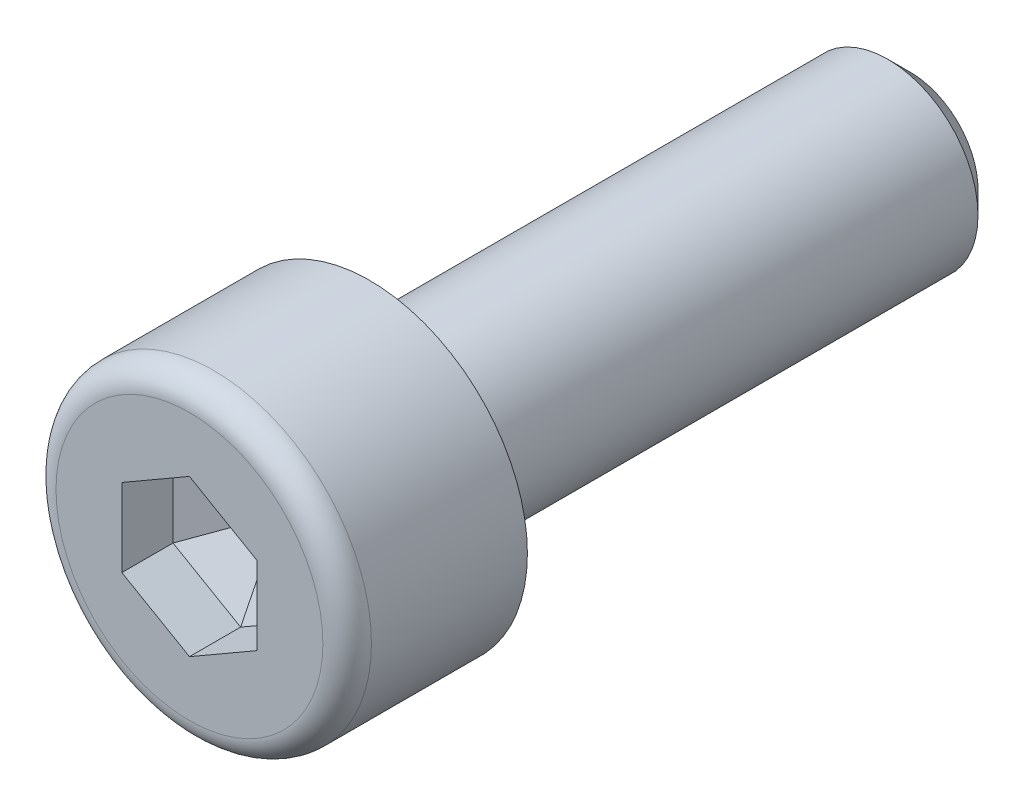
SolidWorks part; units mm, degrees
material "普通碳钢"
ref_plane "前视基准面" through (0, 0, 0) normal (0, 0, 1) x (1, 0, 0)
ref_plane "上视基准面" through (0, 0, 0) normal (0, 1, 0) x (1, 0, 0)
ref_plane "右视基准面" through (0, 0, 0) normal (1, 0, 0) x (0, 0, -1)
sketch "草图1" plane through (0, 0, 0) normal (0, 0, 1) x (1, 0, 0)
  circle A0 centre (0, 0) radius 3.5
  dimension "dk" = 7
extrude "凸台-拉伸1" add sketch "草图1" along normal blind 4
ref_axis "基准轴1" through (0, 0, 4) along (0, 0, -1)
sketch "草图2" plane through (0, 0, 4) normal (0, 0, 1) x (1, 0, 0)
  line L1 (1.5, 0.866) -> (0, 1.7321)
  line L2 (0, 1.7321) -> (-1.5, 0.866)
  line L3 (-1.5, 0.866) -> (-1.5, -0.866)
  line L4 (-1.5, -0.866) -> (0, -1.7321)
  line L5 (0, -1.7321) -> (1.5, -0.866)
  line L6 (1.5, -0.866) -> (1.5, 0.866)
  circle A0 centre (0, 0) radius 1.5 construction
  dimension "s" = 3
extrude "切除-拉伸1" cut sketch "草图2" against normal blind 2
sketch "草图3" plane through (0, 0, 0) normal (0, 0, -1) x (-1, 0, 0)
  circle A0 centre (0, 0) radius 2
  dimension "d" = 4
extrude "凸台-拉伸2" add sketch "草图3" along normal blind 12
cosmetic thread "装饰螺纹线1" parameters "b"=4.9, "D2"=1.221
chamfer "倒角1" distance 0.5 angle 45 1 edges at (-2, 0, -12)
fillet "圆角1" radius 0.5385 1 edges at (3.5, 0, 4)
chamfer "倒角2" distance 0.8646 angle 60 6 edges at (-1.5, 0, 2) (-0.75, 1.299, 2) (0.75, 1.299, 2) (1.5, 0, 2) (-0.75, -1.299, 2) (0.75, -1.299, 2) first distance on face at (-1.5, 0, 3) first distance on face at (-0.75, 1.299, 3) first distance on face at (0.75, 1.299, 3) first distance on face at (1.5, 0, 3) first distance on face at (-0.75, -1.299, 3) first distance on face at (0.75, -1.299, 3)
fillet "圆角2" radius 0.1 1 edges at (2, 0, 0)
ref_plane "基准面1" through (0, 0, 0) normal (0, 0, -1) x (-1, 0, 0)
equation "\"D1@倒角2\" = \"s@草图2\" / 3.47"
equation "\"D1@圆角1\"= \"dk@草图1\" / 13"
equation "\"D1@倒角1\"= \"d@草图3\" / 8"
equation "\"D1@圆角2\"= \"d@草图3\" / \"d@草图3\" * 0.1"
